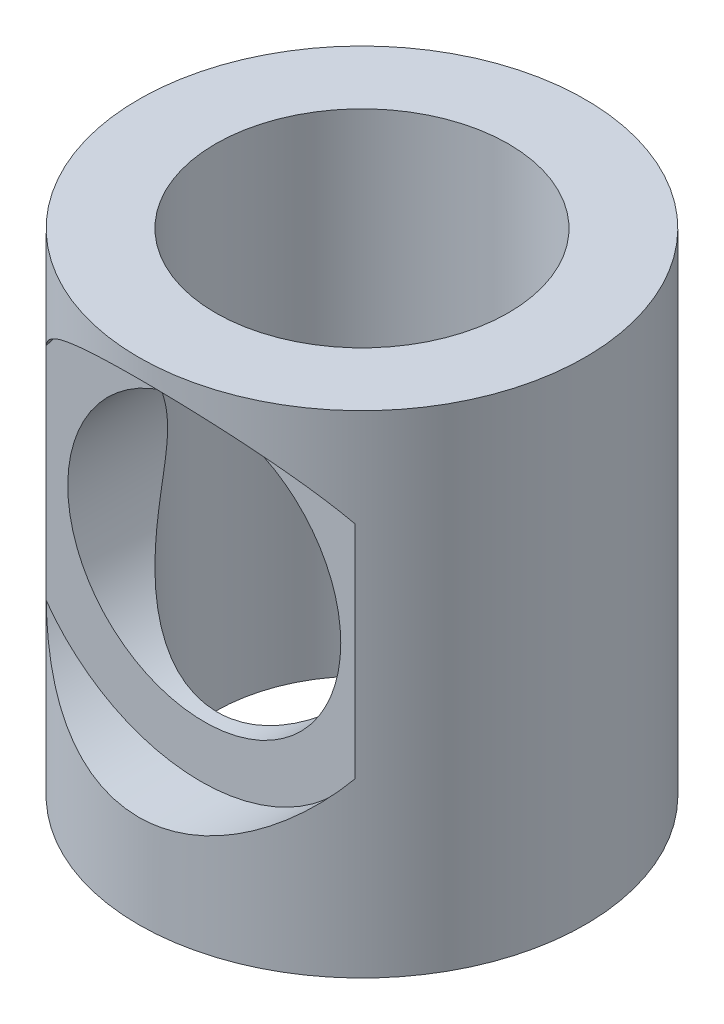
SolidWorks part; units mm, degrees
material "OMD-98"
ref_plane "Front Plane" through (0, 0, 0) normal (0, 0, 1) x (1, 0, 0)
ref_plane "Top Plane" through (0, 0, 0) normal (0, 1, 0) x (1, 0, 0)
ref_plane "Right Plane" through (0, 0, 0) normal (1, 0, 0) x (0, 0, -1)
sketch "Sketch1" plane through (0, 0, 0) normal (0, 1, 0) x (1, 0, 0)
  circle A0 centre (0, 0) radius 9
  circle A1 centre (0, 0) radius 5.9
  dimension "D1" = 18
  dimension "D2" = 11.8
extrude "Boss-Extrude1" add sketch "Sketch1" against normal blind 19.8
sketch "Sketch3" plane through (0, 0, 0) normal (0, 0, 1) x (1, 0, 0)
  line L1 (5.9, 0) -> (-5.9, 0) construction
  circle A0 centre (0, -8.4) radius 7.65
  point P4 (0, -8.4)
  point P5 (0, 0)
  dimension "D1" = 15.3
  dimension "D2" = 8.4
extrude "Cut-Extrude5" cut sketch "Sketch3" along normal through all from offset 6.5
sketch "Sketch6" plane through (0, 0, 6.5) normal (0, 0, 1) x (1, 0, 0)
  line L0 (-6.2249, -19.8) -> (6.2249, -19.8) construction
  line L1 (6.2249, 0) -> (6.2249, -19.8) construction
  circle A0 centre (0.1455, -8.4) radius 5.5
  dimension "D1" = 11
  dimension "D2" = 11.4
  dimension "D3" = 6.0795
extrude "Cut-Extrude6" cut sketch "Sketch6" against normal blind 7 and the other way through all
